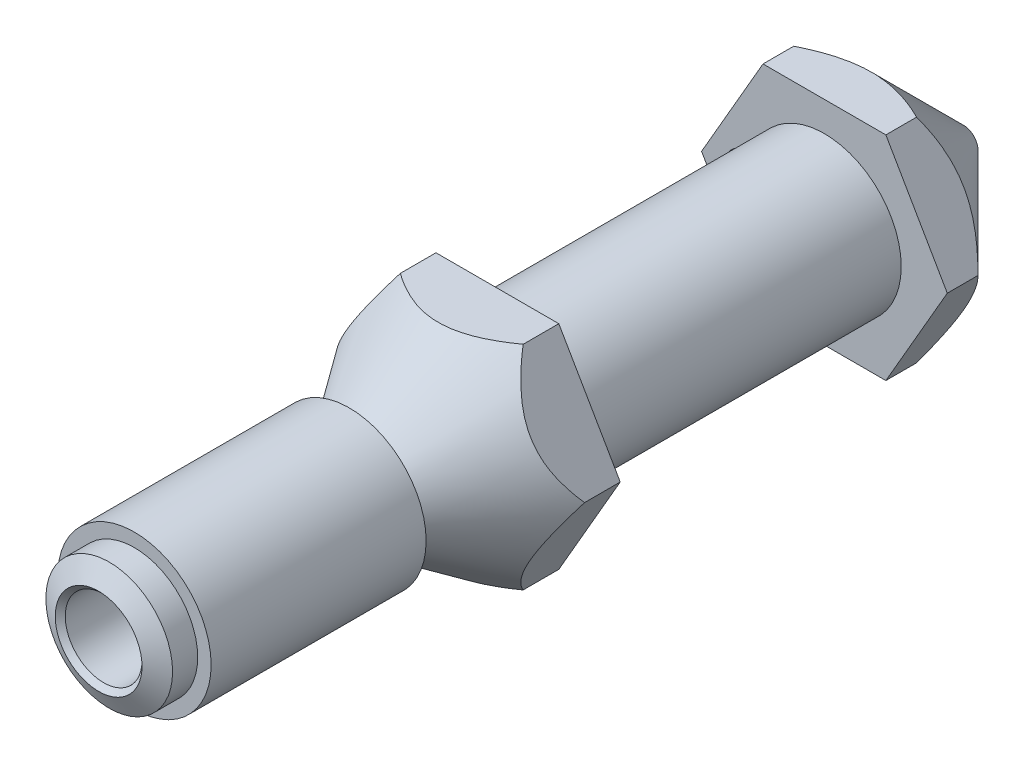
SolidWorks part; units mm, degrees
material "AISI 316 Annealed Stainless Steel Bar (SS)"
ref_plane "Front Plane" through (0, 0, 0) normal (0, 0, 1) x (1, 0, 0)
ref_plane "Top Plane" through (0, 0, 0) normal (0, 1, 0) x (1, 0, 0)
ref_plane "Right Plane" through (0, 0, 0) normal (1, 0, 0) x (0, 0, -1)
sketch "Sketch1" plane through (0, 0, 0) normal (0, -1, 0) x (1, 0, 0)
  line L0 (0, 13.7824) -> (0, -23.8998)
  line L1 (-2, 3.3147) -> (-2, -2.2853)
  line L2 (-3.5, -15.1603) -> (-3.5, -14.6603)
  line L3 (-1, 4.1147) -> (-1.1306, 4.2453)
  line L4 (-3.5, -14.6603) -> (-2, -14.6603)
  line L5 (-2, -14.6603) -> (-2, -6.1415)
  line L6 (-2, -6.1415) -> (-3.5, -6.1415)
  line L7 (-3.5, -6.1415) -> (-3.5, -5.6415)
  line L8 (-2, 3.3147) -> (-1.65, 3.3147)
  line L9 (-1, -16.7603) -> (-1, 4.1147)
  line L10 (-1.1306, 4.2453) -> (-1.65, 3.9691)
  line L12 (-0.175, -18.2853) -> (-0.375, -18.2853)
  line L16 (-0.375, -18.2853) -> (-3.5, -15.1603)
  line L17 (-1.65, 3.3147) -> (-1.65, 3.9691)
  line L19 (-0.175, -18.2853) -> (-0.175, -17.5853)
  line L20 (-0.175, -17.5853) -> (-1, -16.7603)
  line L21 (-2, -2.2853) -> (-1.15, -2.2853)
  line L22 (-1.15, -2.2853) -> (-3.5, -5.6415)
  point P14 (-1, 4.3147)
  dimension "D1" = 1
  dimension "D2" = 2
  dimension "D3" = 16
  dimension "D4" = 5.6
  dimension "D5" = 0.15
  dimension "D6" = 0.2
  dimension "D7" = 45
  dimension "D8" = 0.375
  dimension "D9" = 0.175
  dimension "D10" = 45
  dimension "D11" = 55
  dimension "D12" = 45
  dimension "D13" = 118
  dimension "D14" = 3.5
  dimension "D15" = 0.35
  dimension "D16" = 0.5
  dimension "D17" = 0.5
  dimension "D18" = 1
  dimension "D19" = 0.7
  dimension "D20" = 1.5
revolve "Revolve1" add sketch "Sketch1" angle 360 about L0 region at (-1.6438, 0, -7.5596)
cosmetic thread "Cosmetic Thread1" parameters "D1"=5.6, "D2"=3.22
fillet "Fillet1" radius 0.05 1 edges at (1.15, 0, -2.2853)
sketch "Sketch2" plane through (0, 0, -14.6603) normal (0, 0, 1) x (1, 0, 0)
  circle A0 centre (-2, 0) radius 0.6
  circle A1 centre (0, 0) radius 2 construction
  dimension "D1" = 1.2
extrude "Cut-Extrude1" cut sketch "Sketch2" against normal blind 10 and the other way up to surface (8.5189 mm away) other way up to face at (3.5, 0, -6.1415)
sketch "Sketch3" plane through (0, 0, -6.1415) normal (0, 0, -1) x (-1, 0, 0)
  line L1 (-1.6, 2.7713) -> (-3.2, 0)
  line L2 (-3.2, 0) -> (-1.6, -2.7713)
  line L3 (-1.6, -2.7713) -> (1.6, -2.7713)
  line L4 (1.6, -2.7713) -> (3.2, 0)
  line L5 (3.2, 0) -> (1.6, 2.7713)
  line L6 (1.6, 2.7713) -> (-1.6, 2.7713)
  line L7 (4.0826, -3.7603) -> (-4.0826, -3.7603)
  line L8 (4.0826, -3.7603) -> (4.0826, 3.7603)
  line L9 (4.0826, 3.7603) -> (-4.0826, 3.7603)
  line L10 (-4.0826, -3.7603) -> (-4.0826, 3.7603)
  line L11 (4.0826, -3.7603) -> (-4.0826, 3.7603) construction
  line L12 (4.0826, 3.7603) -> (-4.0826, -3.7603) construction
  circle A0 centre (0, 0) radius 3.2 construction
  dimension "D1" = 6.4
extrude "Cut-Extrude2" cut sketch "Sketch3" against normal blind 10 and the other way blind 40
equation "\"D9@Sketch1\"=0.35/2"
